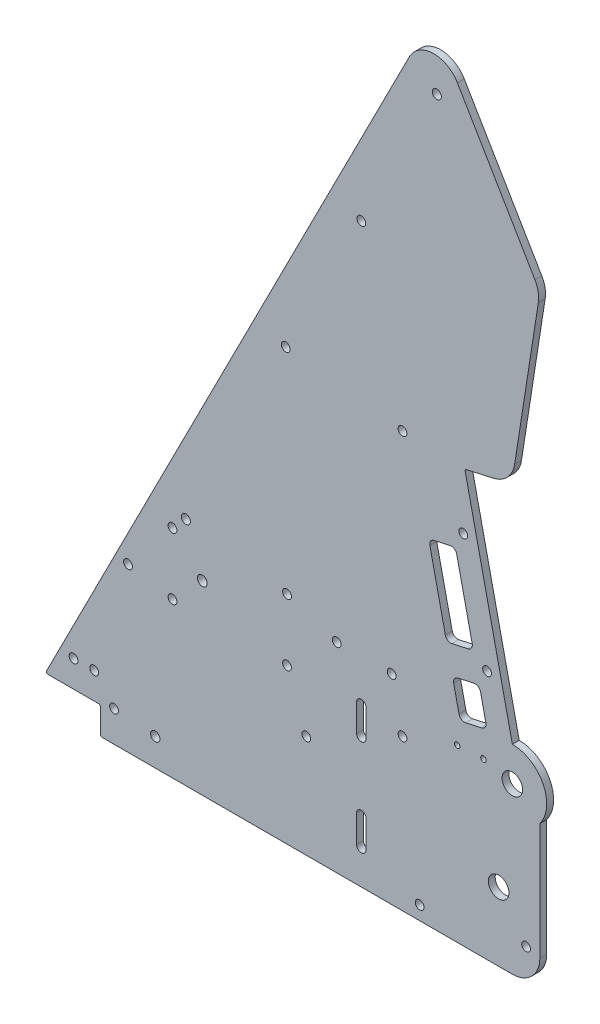
SolidWorks part; units mm, degrees
other "Markup1"
sketch "Sketch5"
ref_plane "Front Plane" through (0, 0, 0) normal (0, 0, 1) x (1, 0, 0)
ref_plane "Top Plane" through (0, 0, 0) normal (0, 1, 0) x (1, 0, 0)
ref_plane "Right Plane" through (0, 0, 0) normal (1, 0, 0) x (0, 0, -1)
sketch "Sketch1" plane through (0, 0, 0) normal (0, 0, 1) x (1, 0, 0)
  line L1 (228.6, -12.7) -> (228.6, 53.975)
  line L2 (178.7547, 351.4131) -> (0, 0)
  line L3 (228.6, 266.7) -> (178.7547, 351.4131)
  line L5 (0, 0) -> (25.4, 0)
  line L6 (25.4, 0) -> (25.4, -12.7)
  line L7 (25.4, -12.7) -> (228.6, -12.7)
  line L9 (215.9, 79.375) -> (193.9097, 178.5667)
  line L10 (193.9097, 178.5667) -> (215.6079, 183.377)
  line L11 (215.6079, 183.377) -> (228.6, 266.7)
  arc A0 (228.6, 53.975) -> (215.9, 79.375) centre (215.9, 63.5) ccw
  dimension "D7" = 12.7
  dimension "D8" = 76.2
  dimension "D10" = 31.75
  dimension "D2" = 279.4
  dimension "D3" = 25.4
  dimension "D4" = 215.9
  dimension "D5" = 394.2644
  dimension "D6" = 203.2
  dimension "D9" = 63.039
  dimension "D11" = 101.6
  dimension "D12" = 12.5
  dimension "D13" = 22.225
extrude "Boss-Extrude1" add sketch "Sketch1" along normal blind 3.175
sketch "Sketch2" plane through (0, 0, 3.175) normal (0, 0, 1) x (1, 0, 0)
  line L0 (178.7547, 351.4131) -> (0, 0) construction
  line L1 (25.4, -12.7) -> (228.6, -12.7) construction
  line L2 (215.9, 79.375) -> (193.9097, 178.5667) construction
  line L3 (193.9097, 178.5667) -> (215.6079, 183.377) construction
  line L4 (215.9, 79.375) -> (193.9097, 178.5667) construction
  line L5 (64.9432, 94.0578) -> (72.5445, 73.1732) construction
  line L6 (64.9432, 94.0578) -> (103.3734, 94.0578) construction
  line L10 (228.6, -12.7) -> (228.6, 53.975) construction
  circle A0 centre (64.9432, 94.0578) radius 2.0955
  circle A1 centre (180.975, 322.1643) radius 2.0955
  circle A2 centre (72.5445, 73.1732) radius 2.286
  circle A3 centre (193.2078, 152.3944) radius 2.032
  circle A4 centre (215.9, 63.5) radius 4.7625
  circle A7 centre (173.0375, -6.35) radius 2.032
  circle A8 centre (204.203, 102.7985) radius 2.032
  circle A26 centre (209.55, 19.05) radius 4.7625
  arc A30 (228.6, 53.975) -> (215.9, 79.375) centre (215.9, 63.5) ccw construction
  circle A31 centre (165.1, 179.3875) radius 2.032
  circle A35 centre (111.724, 87.4607) radius 2.032
  circle A36 centre (111.724, 58.8857) radius 2.032
  circle A37 centre (58.765, 58.8857) radius 2.032
  circle A38 centre (58.765, 87.4607) radius 2.032
  circle A39 centre (111.724, 58.8857) radius 1.905 construction
  circle A42 centre (111.724, 87.4607) radius 1.905 construction
  circle A43 centre (58.765, 58.8857) radius 1.905 construction
  circle A44 centre (58.765, 87.4607) radius 1.905 construction
  dimension "D3" = 4.191
  dimension "D5" = 4.191
  dimension "D9" = 4.572
  dimension "D20" = 9.525
  dimension "D23" = 9.525
  dimension "D18" = 4.064
  dimension "D26" = 4.064
  dimension "D14" = 4.064
  dimension "D10" = 4.064
  dimension "D2" = 15.24
  dimension "D6" = 15.24
  dimension "D7" = 22.225
  dimension "D21" = 44.45
  dimension "D22" = 6.35
  dimension "D19" = 160.3375
  dimension "D24" = 44.45
  dimension "D25" = 6.35
  dimension "D27" = 25.4
  dimension "D28" = 50.8
  dimension "D29" = 6.35
  dimension "D17" = 6.35
  dimension "D33" = 55.5625
  dimension "D15" = 114.3
  dimension "D4" = 180.975
  dimension "D8" = 70
extrude "Cut-Extrude1" cut sketch "Sketch2" against normal through all
sketch "Sketch7" plane through (0, 0, 3.175) normal (0, 0, 1) x (1, 0, 0)
  line L0 (146.05, 3.175) -> (146.05, 15.875) construction
  line L1 (143.891, 3.175) -> (143.891, 15.875)
  line L2 (148.209, 3.175) -> (148.209, 15.875)
  line L3 (146.05, 47.625) -> (146.05, 60.325) construction
  line L4 (143.891, 47.625) -> (143.891, 60.325)
  line L5 (148.209, 47.625) -> (148.209, 60.325)
  line L6 (25.4, -12.7) -> (228.6, -12.7) construction
  line L12 (228.6, -12.7) -> (228.6, 53.975) construction
  line L13 (25.4, -12.7) -> (228.6, -12.7) construction
  arc A0 (143.891, 3.175) -> (148.209, 3.175) centre (146.05, 3.175) ccw
  arc A1 (148.209, 15.875) -> (143.891, 15.875) centre (146.05, 15.875) ccw
  arc A2 (143.891, 47.625) -> (148.209, 47.625) centre (146.05, 47.625) ccw
  arc A3 (148.209, 60.325) -> (143.891, 60.325) centre (146.05, 60.325) ccw
  circle A8 centre (50.8, 0) radius 2.159
  point P2 (146.05, 9.525)
  point P9 (146.05, 53.975)
  dimension "D1" = 4.318
  dimension "D5" = 4.318
  dimension "D2" = 12.7
  dimension "D3" = 12.7
  dimension "D4" = 44.45
  dimension "D6" = 95.25
  dimension "D7" = 82.55
  dimension "D8" = 15.875
  dimension "D9" = 12.7
extrude "Cut-Extrude2" cut sketch "Sketch7" against normal through all
sketch "Sketch10" plane through (0, 0, 3.175) normal (0, 0, 1) x (1, 0, 0)
  circle A0 centre (120.65, 34.925) radius 2.032
  circle A1 centre (165.1, 57.15) radius 2.032
  circle A2 centre (13.0465, 12.3347) radius 2.032
  circle A3 centre (22.5715, 12.3347) radius 2.032
  circle A4 centre (38.2114, 62.6398) radius 2.032
  dimension "D1" = 4.064
  dimension "D3" = 34.925
  dimension "D2" = 120.65
  dimension "D4" = 63.5
  dimension "D5" = 69.85
extrude "Cut-Extrude3" cut sketch "Sketch10" against normal up to next
fillet "Fillet1" radius 12.7 4 edges at (228.6, -12.7, 1.5875) (178.7547, 351.4131, 1.5875) (215.6079, 183.377, 1.5875) (228.6, 266.7, 1.5875)
fillet "Fillet2" radius 0.7937 4 edges at (25.4, -12.7, 1.5875) (25.4, 0, 1.5875) (193.9097, 178.5667, 1.5875) (0, 0, 1.5875)
sketch "Sketch12" plane through (0, 0, 3.175) normal (0, 0, 1) x (1, 0, 0)
  circle A0 centre (31.75, 1.5875) radius 2.032
  circle A1 centre (173.0375, -6.35) radius 2.032
  circle A2 centre (222.25, 1.5875) radius 2.032
  dimension "D1" = 4.064
extrude "Cut-Extrude5" cut sketch "Sketch12" against normal through all
sketch "Sketch13" plane through (0, 0, 3.175) normal (0, 0, 1) x (1, 0, 0)
  line L1 (228.6, 0) -> (228.6, 53.975) construction
  line L2 (1.2943, 0) -> (24.6062, 0) construction
  line L3 (26.1937, -12.7) -> (215.9, -12.7) construction
  circle A0 centre (111.125, 186.055) radius 2.032
  circle A1 centre (146.05, 254) radius 2.032
  dimension "D2" = 4.064
  dimension "D5" = 4.064
  dimension "D1" = 198.755
  dimension "D3" = 82.55
  dimension "D4" = 254
  dimension "D6" = 117.475
extrude "Cut-Extrude6" cut sketch "Sketch13" against normal through all
sketch "Sketch14" plane through (0, 0, 3.175) normal (0, 0, 1) x (1, 0, 0)
  line L0 (177.2237, 142.3466) -> (189.6226, 145.0954)
  line L1 (189.6226, 145.0954) -> (197.869, 107.8985)
  line L2 (197.869, 107.8985) -> (185.47, 105.1497)
  line L3 (185.47, 105.1497) -> (177.2237, 142.3466)
  line L4 (187.1428, 144.5456) -> (179.7035, 142.8963) construction
  line L5 (188.2188, 92.7508) -> (200.6178, 95.4995)
  line L6 (188.2188, 92.7508) -> (191.7922, 76.6321)
  line L7 (191.7922, 76.6321) -> (204.1912, 79.3809)
  line L8 (200.6178, 95.4995) -> (204.1912, 79.3809)
  line L11 (197.3192, 110.3783) -> (190.1724, 142.6156) construction
  line L12 (177.7734, 139.8668) -> (184.9203, 107.6295) construction
  line L13 (187.9498, 105.6995) -> (195.3892, 107.3487) construction
  line L14 (203.6414, 81.8607) -> (201.1675, 93.0197) construction
  line L15 (194.272, 77.1819) -> (201.7114, 78.8311) construction
  line L16 (188.7686, 90.271) -> (191.2425, 79.1119) construction
  line L17 (198.138, 94.9498) -> (190.6986, 93.3005) construction
  circle A0 centre (190.4268, 66.2609) radius 1.27
  circle A1 centre (202.5335, 66.7895) radius 1.27
  circle A2 centre (190.4268, 66.2609) radius 1.27 construction
  circle A3 centre (202.5335, 66.7895) radius 1.27 construction
  circle A4 centre (160.111, 79.6925) radius 2.032
  circle A5 centre (134.711, 79.6925) radius 2.032
  point P8 (152.4, 88.9)
  dimension "D1" = 4.064
extrude "Cut-Extrude7" cut sketch "Sketch14" against normal through all both and the other way through all
fillet "Fillet3" radius 2.54 8 edges at (200.6178, 95.4995, 1.5875) (188.2188, 92.7508, 1.5875) (191.7922, 76.6321, 1.5875) (204.1912, 79.3809, 1.5875) (197.869, 107.8985, 1.5875) (185.47, 105.1497, 1.5875) (177.2237, 142.3466, 1.5875) (189.6226, 145.0954, 1.5875)
equation "\"D6@Sketch2\"=\"D2@Sketch2\""
